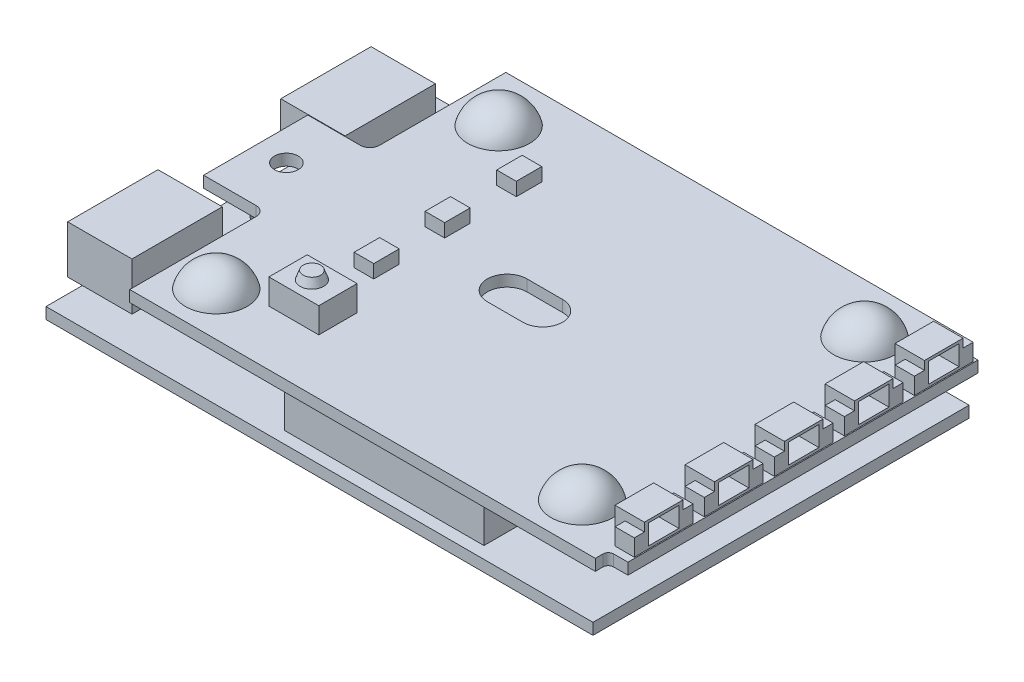
SolidWorks part; units mm, degrees
ref_plane "Front Plane" through (0, 0, 0) normal (0, 0, 1) x (1, 0, 0)
ref_plane "Top Plane" through (0, 0, 0) normal (0, 1, 0) x (1, 0, 0)
ref_plane "Right Plane" through (0, 0, 0) normal (1, 0, 0) x (0, 0, -1)
sketch "Sketch1" plane through (0, 0, 0) normal (0, 1, 0) x (1, 0, 0)
  line L1 (0, 0) -> (77.978, 0)
  line L2 (0, 0) -> (0, -53.6194)
  line L3 (0, -53.6194) -> (77.978, -53.6194)
  line L4 (77.978, 0) -> (77.978, -53.6194)
  dimension "D1" = 77.978
  dimension "D2" = 53.6194
extrude "Bottom Board" add sketch "Sketch1" along normal blind 1.6129
sketch "Sketch2" plane through (0, 1.6129, 0) normal (0, 1, 0) x (-1, 0, 0)
  line L0 (0, 0) -> (0, 53.6194) construction
  line L1 (2.0955, 5.1816) -> (-7.0739, 5.1816)
  line L2 (2.0955, 5.1816) -> (2.0955, 18.0594)
  line L3 (2.0955, 18.0594) -> (-7.0739, 18.0594)
  line L4 (-7.0739, 5.1816) -> (-7.0739, 18.0594)
  line L5 (-77.978, 0) -> (0, 0) construction
  dimension "D1" = 12.8778
  dimension "D2" = 9.1694
  dimension "D3" = 5.1816
  dimension "D4" = 2.0955
extrude "Connector Body" add sketch "Sketch2" along normal blind 6.8199
sketch "Sketch4" plane through (-2.0955, 0, 0) normal (-1, 0, 0) x (0, 0, 1)
  line L0 (5.1816, 8.4328) -> (5.1816, 1.6129) construction
  line L1 (5.7658, 7.8105) -> (8.3947, 7.8105)
  line L2 (5.7658, 7.8105) -> (5.7658, 5.2197)
  line L3 (5.7658, 5.2197) -> (8.3947, 5.2197)
  line L4 (8.3947, 7.8105) -> (8.3947, 5.2197)
  line L5 (5.1816, 8.4328) -> (18.0594, 8.4328) construction
  line L6 (8.7926, 7.8105) -> (8.7926, 5.2197)
  line L7 (8.7926, 5.2197) -> (11.4215, 5.2197)
  line L8 (11.4215, 7.8105) -> (11.4215, 5.2197)
  line L9 (8.7926, 7.8105) -> (11.4215, 7.8105)
  line L10 (11.8195, 7.8105) -> (11.8195, 5.2197)
  line L11 (11.8195, 5.2197) -> (14.4484, 5.2197)
  line L12 (14.4484, 7.8105) -> (14.4484, 5.2197)
  line L13 (11.8195, 7.8105) -> (14.4484, 7.8105)
  line L14 (14.8463, 7.8105) -> (14.8463, 5.2197)
  line L15 (14.8463, 5.2197) -> (17.4752, 5.2197)
  line L16 (17.4752, 7.8105) -> (17.4752, 5.2197)
  line L17 (14.8463, 7.8105) -> (17.4752, 7.8105)
  line L18 (5.7658, 4.826) -> (5.7658, 2.2352)
  line L19 (5.7658, 2.2352) -> (8.3947, 2.2352)
  line L20 (8.3947, 4.826) -> (8.3947, 2.2352)
  line L21 (5.7658, 4.826) -> (8.3947, 4.826)
  line L22 (8.7926, 4.826) -> (8.7926, 2.2352)
  line L23 (8.7926, 2.2352) -> (11.4215, 2.2352)
  line L24 (11.4215, 4.826) -> (11.4215, 2.2352)
  line L25 (8.7926, 4.826) -> (11.4215, 4.826)
  line L26 (11.8195, 4.826) -> (11.8195, 2.2352)
  line L27 (11.8195, 2.2352) -> (14.4484, 2.2352)
  line L28 (14.4484, 4.826) -> (14.4484, 2.2352)
  line L29 (11.8195, 4.826) -> (14.4484, 4.826)
  line L30 (14.8463, 4.826) -> (14.8463, 2.2352)
  line L31 (14.8463, 2.2352) -> (17.4752, 2.2352)
  line L32 (17.4752, 4.826) -> (17.4752, 2.2352)
  line L33 (14.8463, 4.826) -> (17.4752, 4.826)
  line L34 (18.0594, 8.4328) -> (18.0594, 1.6129) construction
  line L35 (17.4752, 7.4085) -> (18.0594, 7.4085) construction
  line L36 (5.7658, 7.5345) -> (5.1816, 7.5345) construction
  line L37 (7.8077, 7.8105) -> (7.8077, 8.4328)
  line L38 (7.8077, 2.2352) -> (7.8077, 1.6129)
  line L39 (5.1816, 1.6129) -> (18.0594, 1.6129) construction
  dimension "D1" = 2.6289
  dimension "D2" = 2.5908
  dimension "D3" = 0.5842
  dimension "D4" = 0.6223
  dimension "D5" = 4
  dimension "D6" = 2
extrude "Connector Holes" cut sketch "Sketch4" against normal blind 5.08 contours L4 L1 L2 L3 | L9 L6 L7 L8 | L13 L10 L11 L12 | L17 L14 L15 L16 | L33 L30 L31 L32 | L29 L26 L27 L28 | L25 L22 L23 L24 | L21 L18 L19 L20 region at (-2.0955, 6.5151, 7.0802) region at (-2.0955, 6.5151, 10.1071) region at (-2.0955, 6.5151, 13.1339) region at (-2.0955, 6.5151, 16.1608) region at (-2.0955, 3.5306, 7.0802) region at (-2.0955, 3.5306, 10.1071) region at (-2.0955, 3.5306, 13.1339) region at (-2.0955, 3.5306, 16.1608)
ref_plane "Center Plane" through (0, 0, 26.8097) normal (0, 0, -1) x (-1, 0, 0)
mirror "Connector Mirror" about plane through (0, 0, 26.8097) normal (0, 0, -1) of "Connector Holes", "Connector Body"
sketch "Sketch5" plane through (0, 1.6129, 0) normal (0, 1, 0) x (1, 0, 0)
  line L0 (77.978, -26.8097) -> (0, -26.8097) construction
  line L1 (77.978, -53.6194) -> (77.978, 0) construction
  line L2 (0, -18.0594) -> (0, -35.56) construction
  line L3 (2.9845, -26.8097) -> (2.9845, -21.4955) construction
  line L4 (36.0172, -26.8097) -> (36.0172, -8.1241) construction
  line L5 (0, -18.0594) -> (0, -35.56) construction
  circle A0 centre (4.68, -26.8097) radius 1.6955
  circle A1 centre (39.0652, -26.8097) radius 3.048
  dimension "D1" = 3.3909
  dimension "D3" = 6.096
  dimension "D2" = 2.9845
  dimension "D4" = 36.0172
extrude "Bottom Board Hole" cut sketch "Sketch5" against normal up to next
sketch "Sketch6" plane through (0, 1.6129, 0) normal (0, 1, 0) x (-1, 0, 0)
  line L0 (-77.978, 0) -> (0, 0) construction
  line L1 (-39.37, 1.7018) -> (-67.818, 1.7018)
  line L2 (-39.37, 1.7018) -> (-39.37, 7.2644)
  line L3 (-39.37, 7.2644) -> (-67.818, 7.2644)
  line L4 (-67.818, 1.7018) -> (-67.818, 7.2644)
  line L5 (-77.978, 53.6194) -> (-77.978, 0) construction
  line L6 (-32.2834, 46.355) -> (-60.7314, 46.355)
  line L7 (-32.2834, 46.355) -> (-32.2834, 51.9176)
  line L8 (-32.2834, 51.9176) -> (-60.7314, 51.9176)
  line L9 (-60.7314, 46.355) -> (-60.7314, 51.9176)
  line L10 (0, 18.0594) -> (0, 35.56) construction
  line L12 (-44.4047, 1.7018) -> (-44.4047, 0) construction
  line L13 (-37.561, 51.9176) -> (-37.561, 53.6194) construction
  line L14 (0, 53.6194) -> (-77.978, 53.6194) construction
  dimension "D1" = 28.448
  dimension "D2" = 5.5626
  dimension "D3" = 1.7018
  dimension "D4" = 10.16
  dimension "D5" = 28.448
  dimension "D6" = 5.5626
  dimension "D7" = 32.2834
extrude "Layer Connectors" add sketch "Sketch6" along normal blind 6.4516
sketch "Sketch7" plane through (0, 8.0645, 0) normal (0, 1, 0) x (1, 0, 0)
  line L0 (77.978, -53.6194) -> (77.978, 0) construction
  line L1 (78.3082, 0) -> (11.938, 0)
  line L2 (81.1022, -1.8542) -> (81.1022, -51.7652)
  line L3 (78.3082, -53.6194) -> (11.938, -53.6194)
  line L4 (11.938, 0) -> (11.938, -18.0086)
  line L5 (0, -18.0594) -> (0, -35.56) construction
  line L6 (77.978, 0) -> (0, 0) construction
  line L7 (0, -53.6194) -> (77.978, -53.6194) construction
  line L8 (15.6034, 0) -> (15.6034, -19.3802) construction
  line L9 (10.5664, -19.3802) -> (3.0861, -19.3802)
  line L10 (11.938, -35.6108) -> (11.938, -53.6194)
  line L11 (10.5664, -34.2392) -> (3.0861, -34.2392)
  line L12 (3.0861, -19.3802) -> (3.0861, -34.2392)
  line L13 (10.5664, -19.3802) -> (15.6034, -19.3802) construction
  line L14 (16.8171, -34.2392) -> (16.8171, -53.6194) construction
  line L15 (10.5664, -34.2392) -> (16.8171, -34.2392) construction
  line L16 (77.978, -26.8097) -> (0, -26.8097) construction
  line L17 (5.7658, -26.8097) -> (5.7658, -22.9762) construction
  line L18 (36.1061, -26.8097) -> (46.8249, -26.8097) construction
  line L19 (38.9318, -23.984) -> (43.9992, -23.984)
  line L20 (36.1061, -26.8097) -> (36.1061, -33.1542) construction
  line L21 (38.9318, -29.6354) -> (43.9992, -29.6355)
  line L22 (78.3082, -53.6194) -> (78.3082, -52.5272)
  line L23 (81.1022, -51.7652) -> (79.0702, -51.7652)
  line L25 (81.1022, -1.8542) -> (79.0702, -1.8542)
  line L26 (78.3082, 0) -> (78.3082, -1.0922)
  arc A0 (11.938, -18.0086) -> (10.5664, -19.3802) centre (10.5664, -18.0086) cw
  arc A1 (10.5664, -34.2392) -> (11.938, -35.6108) centre (10.5664, -35.6108) cw
  circle A2 centre (7.4613, -26.8097) radius 1.6955
  circle A3 centre (4.68, -26.8097) radius 1.6955 construction
  arc A4 (38.9318, -29.6354) -> (38.9318, -23.984) centre (38.9318, -26.8097) cw
  arc A5 (43.9992, -23.984) -> (43.9992, -29.6355) centre (43.9992, -26.8097) cw
  arc A6 (79.0702, -1.8542) -> (78.3082, -1.0922) centre (79.0702, -1.0922) cw
  arc A7 (79.0702, -51.7652) -> (78.3082, -52.5272) centre (79.0702, -52.5272) ccw
  point P45 (78.3082, -1.8542)
  dimension "D5" = 1.3716
  dimension "D6" = 1.3716
  dimension "D13" = 0.762
  dimension "D1" = 3.1242
  dimension "D2" = 11.938
  dimension "D3" = 19.3802
  dimension "D4" = 3.0861
  dimension "D7" = 2.6797
  dimension "D8" = 5.6515
  dimension "D9" = 10.7188
  dimension "D10" = 33.02
  dimension "D11" = 2.794
  dimension "D12" = 1.8542
extrude "Top Board" add sketch "Sketch7" along normal blind 1.6129
sketch "Sketch8" plane through (0, 9.6774, 0) normal (0, 1, 0) x (1, 0, 0)
  line L1 (80.9498, -2.3876) -> (78.2066, -2.3876)
  line L2 (80.9498, -2.3876) -> (80.9498, -10.7696)
  line L3 (80.9498, -10.7696) -> (78.2066, -10.7696)
  line L4 (78.2066, -2.3876) -> (78.2066, -10.7696)
  line L5 (78.3082, 0) -> (11.938, 0) construction
  line L6 (81.1022, -51.7652) -> (81.1022, -1.8542) construction
  dimension "D1" = 2.7432
  dimension "D2" = 8.382
  dimension "D3" = 2.3876
  dimension "D4" = 0.1524
extrude "Maker Connector Sides" add sketch "Sketch8" along normal blind 2.3876
sketch "Sketch9" plane through (0, 12.065, 0) normal (0, 1, 0) x (1, 0, 0)
  line L0 (80.9498, -10.7696) -> (80.9498, -2.3876) construction
  line L1 (80.9498, -3.8227) -> (76.7588, -3.8227)
  line L2 (80.9498, -3.8227) -> (80.9498, -9.3345)
  line L3 (80.9498, -9.3345) -> (76.7588, -9.3345)
  line L4 (76.7588, -3.8227) -> (76.7588, -9.3345)
  line L6 (78.7411, -2.3876) -> (78.7411, -3.8227) construction
  line L7 (80.9498, -2.3876) -> (78.2066, -2.3876) construction
  line L9 (78.7411, -9.3345) -> (78.7411, -10.7696) construction
  line L10 (78.2066, -10.7696) -> (80.9498, -10.7696) construction
  point P12 (63.292, 1.2113)
  dimension "D1" = 5.5118
  dimension "D2" = 4.191
extrude "Marker Connector Box" add sketch "Sketch9" along normal blind 1.2192
sketch "Sketch10" plane through (0, 9.6774, 0) normal (0, 1, 0) x (1, 0, 0)
  line L0 (76.7588, -9.3345) -> (78.2066, -9.3345) construction
  line L1 (78.2066, -3.8227) -> (76.7588, -3.8227) construction
  line L2 (76.7588, -3.8227) -> (76.7588, -9.3345) construction
  line L3 (76.7588, -9.3345) -> (78.2066, -9.3345)
  line L4 (78.2066, -3.8227) -> (76.7588, -3.8227)
  line L5 (76.7588, -3.8227) -> (76.7588, -9.3345)
  line L10 (78.2066, -3.8227) -> (76.7588, -3.8227)
  line L11 (78.2066, -9.3345) -> (78.2066, -3.8227)
  line L12 (76.7588, -9.3345) -> (78.2066, -9.3345)
  line L13 (76.7588, -3.8227) -> (76.7588, -9.3345)
  line L14 (78.2066, -3.8227) -> (76.7588, -3.8227)
  line L15 (78.2066, -9.3345) -> (78.2066, -3.8227)
  line L16 (76.7588, -9.3345) -> (78.2066, -9.3345)
  line L17 (76.7588, -3.8227) -> (76.7588, -9.3345)
  line M11 (78.2066, -10.7696) -> (78.2066, -2.3876)
  dimension "D1" = 0
extrude "Marker Connector Rear" add sketch "Sketch10" along normal up to body contours L4 L5 L3 M11 region at (77.4827, 9.6774, 6.5786)
sketch "Sketch11" plane through (81.1022, 0, 0) normal (1, 0, 0) x (0, 0, -1)
  line L0 (-9.3345, 13.2842) -> (-9.3345, 12.065) construction
  line L1 (-8.7376, 12.9032) -> (-4.4196, 12.9032)
  line L2 (-8.7376, 12.9032) -> (-8.7376, 10.0584)
  line L3 (-8.7376, 10.0584) -> (-4.4196, 10.0584)
  line L4 (-4.4196, 12.9032) -> (-4.4196, 10.0584)
  line L5 (-8.7376, 11.497) -> (-9.3345, 11.497) construction
  line L6 (-4.4196, 12.3526) -> (-3.8227, 12.3526) construction
  line L7 (-3.8227, 13.2842) -> (-3.8227, 12.065) construction
  line L8 (-9.3345, 13.2842) -> (-3.8227, 13.2842) construction
  line L10 (-7.3098, 10.0584) -> (-7.3098, 9.6774) construction
  line L11 (-51.7652, 9.6774) -> (-1.8542, 9.6774) construction
  line L12 (-7.3098, 13.2842) -> (-7.3098, 12.9032) construction
  dimension "D1" = 0.5969
  dimension "D2" = 0.381
extrude "Marker Connector " cut sketch "Sketch11" against normal blind 3.175
pattern_linear "Maker Connectors Pattern" count 5 spacing 9.9822 along (0, 0, 1) of "Marker Connector Box", "Marker Connector ", "Maker Connector Sides", "Marker Connector Rear"
sketch "Sketch12" plane through (0, 9.6774, 0) normal (0, 1, 0) x (-1, 0, 0)
  line L0 (-13.589, 7.0866) -> (-13.589, -6.6902) construction
  line L1 (-11.938, 0) -> (-11.938, 18.0086) construction
  line L2 (-17.9959, 2.6797) -> (-29.745, 2.6797) construction
  line L3 (-78.3082, 0) -> (-11.938, 0) construction
  circle A0 centre (-17.9959, 7.0866) radius 4.4069
  dimension "D1" = 8.8138
  dimension "D2" = 1.651
  dimension "D3" = 2.6797
extrude "Glue Dome" add sketch "Sketch12" along normal blind 3.4036
fillet "Glue Dome Fillet" radius 4.5415 1 edges at (17.9959, 13.081, 11.4935)
pattern_linear "Glue pattern" count 2 spacing 40.259 along (0, 0, 1) count 2 spacing 52.1462 along (1, 0, 0) of "Glue Dome Fillet", "Glue Dome"
sketch "Sketch13" plane through (0, 9.6774, 0) normal (0, 1, 0) x (-1, 0, 0)
  line L0 (-78.3082, 0) -> (-11.938, 0) construction
  line L1 (-25.2349, 10.9728) -> (-28.0289, 10.9728)
  line L2 (-25.2349, 10.9728) -> (-25.2349, 14.605)
  line L3 (-25.2349, 14.605) -> (-28.0289, 14.605)
  line L4 (-28.0289, 10.9728) -> (-28.0289, 14.605)
  line L5 (-3.0861, 19.3802) -> (-3.0861, 34.2392) construction
  line L7 (-25.2349, 21.1836) -> (-28.0289, 21.1836)
  line L8 (-25.2349, 21.1836) -> (-25.2349, 24.8158)
  line L9 (-25.2349, 24.8158) -> (-28.0289, 24.8158)
  line L10 (-28.0289, 21.1836) -> (-28.0289, 24.8158)
  line L11 (-25.2349, 31.2928) -> (-28.0289, 31.2928)
  line L12 (-25.2349, 31.2928) -> (-25.2349, 34.925)
  line L13 (-25.2349, 34.925) -> (-28.0289, 34.925)
  line L14 (-28.0289, 31.2928) -> (-28.0289, 34.925)
  dimension "D1" = 2.794
  dimension "D2" = 3.6322
  dimension "D3" = 10.9728
  dimension "D4" = 22.1488
  dimension "D5" = 24.8158
  dimension "D6" = 34.925
extrude "LEDs" add sketch "Sketch13" along normal blind 1.905
sketch "Sketch14" plane through (0, 9.6774, 0) normal (0, 1, 0) x (-1, 0, 0)
  line L0 (-11.938, 53.6194) -> (-78.3082, 53.6194) construction
  line L1 (-23.9014, 40.2844) -> (-31.0134, 40.2844)
  line L2 (-23.9014, 40.2844) -> (-23.9014, 45.7454)
  line L3 (-23.9014, 45.7454) -> (-31.0134, 45.7454)
  line L4 (-31.0134, 40.2844) -> (-31.0134, 45.7454)
  line L5 (-81.1022, 51.7652) -> (-81.1022, 1.8542) construction
  dimension "D1" = 7.112
  dimension "D2" = 5.461
  dimension "D3" = 7.874
  dimension "D4" = 50.0888
extrude "IR receiver base" add sketch "Sketch14" along normal blind 3.6068
sketch "Sketch16" plane through (0, 13.2842, 0) normal (0, 1, 0) x (-1, 0, 0)
  line L0 (-27.305, 40.2844) -> (-27.305, 45.7454) construction
  line L3 (-31.0134, 40.2844) -> (-23.9014, 40.2844) construction
  line L4 (-23.9014, 45.7454) -> (-31.0134, 45.7454) construction
  line L5 (-28.9814, 43.0149) -> (-28.9814, 38.6964) construction
  line L6 (-23.9014, 40.2844) -> (-23.9014, 45.7454) construction
  circle A0 centre (-27.305, 43.0149) radius 1.6764
  circle A1 centre (-27.305, 43.0149) radius 1.2446 construction
  dimension "D1" = 3.3528
  dimension "D2" = 2.4892
  dimension "D3" = 5.08
ref_plane "Plane for IR receiver" through (0, 14.4526, 0) normal (0, 1, 0) x (-1, 0, 0)
sketch "Sketch17" plane through (0, 14.4526, 0) normal (0, 1, 0) x (-1, 0, 0)
  circle A0 centre (-27.305, 43.0149) radius 1.2446 construction
  circle A3 centre (-27.305, 43.0149) radius 1.2446
loft "IR receiver" add profiles "Sketch16", "Sketch17" connector at (28.1584, 13.2842, 44.4578) connector at (27.9456, 14.4526, 44.082)
sketch "Sketch18" plane through (0, 0, 0) normal (0, -1, 0) x (1, 0, 0)
  line L0 (0, 53.6194) -> (77.978, 53.6194) construction
  line L1 (15.2908, 49.5554) -> (18.0848, 49.5554)
  line L2 (15.2908, 49.5554) -> (15.2908, 44.5262)
  line L3 (15.2908, 44.5262) -> (18.0848, 44.5262)
  line L4 (18.0848, 49.5554) -> (18.0848, 44.5262)
  line L5 (0, 0) -> (0, 53.6194) construction
  line L6 (15.2908, 42.7228) -> (18.0848, 42.7228)
  line L7 (15.2908, 42.7228) -> (15.2908, 37.6936)
  line L8 (15.2908, 37.6936) -> (18.0848, 37.6936)
  line L9 (18.0848, 42.7228) -> (18.0848, 37.6936)
  line L10 (77.978, 0) -> (0, 0) construction
  line L11 (20.32, 36.0934) -> (23.114, 36.0934)
  line L12 (20.32, 36.0934) -> (20.32, 31.0642)
  line L13 (20.32, 31.0642) -> (23.114, 31.0642)
  line L14 (23.114, 36.0934) -> (23.114, 31.0642)
  point P14 (13.9053, 51.0341)
  point P15 (14.7108, 50.9803)
  dimension "D1" = 2.794
  dimension "D2" = 5.0292
  dimension "D3" = 4.064
  dimension "D4" = 15.2908
  dimension "D5" = 2.794
  dimension "D6" = 5.0292
  dimension "D7" = 37.6936
  dimension "D8" = 2.794
  dimension "D9" = 5.0292
  dimension "D10" = 20.32
  dimension "D11" = 17.526
extrude "Back components" add sketch "Sketch18" along normal blind 2.4892
sketch "Sketch19" plane through (0, 0, 0) normal (0, -1, 0) x (1, 0, 0)
  line L0 (0, 53.6194) -> (77.978, 53.6194) construction
  line L1 (36.3093, 43.5864) -> (38.0873, 43.5864)
  line L2 (36.3093, 43.5864) -> (36.3093, 40.513)
  line L3 (36.3093, 40.513) -> (38.0873, 40.513)
  line L4 (38.0873, 43.5864) -> (38.0873, 40.513)
  line L5 (77.978, 53.6194) -> (77.978, 0) construction
  line L6 (40.3606, 37.338) -> (42.1386, 37.338)
  line L7 (40.3606, 37.338) -> (40.3606, 34.2646)
  line L8 (40.3606, 34.2646) -> (42.1386, 34.2646)
  line L9 (42.1386, 37.338) -> (42.1386, 34.2646)
  dimension "D1" = 1.778
  dimension "D2" = 3.0734
  dimension "D3" = 10.033
  dimension "D4" = 39.8907
  dimension "D5" = 1.778
  dimension "D6" = 16.2814
  dimension "D7" = 35.8394
extrude "Bottom caps" add sketch "Sketch19" along normal blind 1.7526
